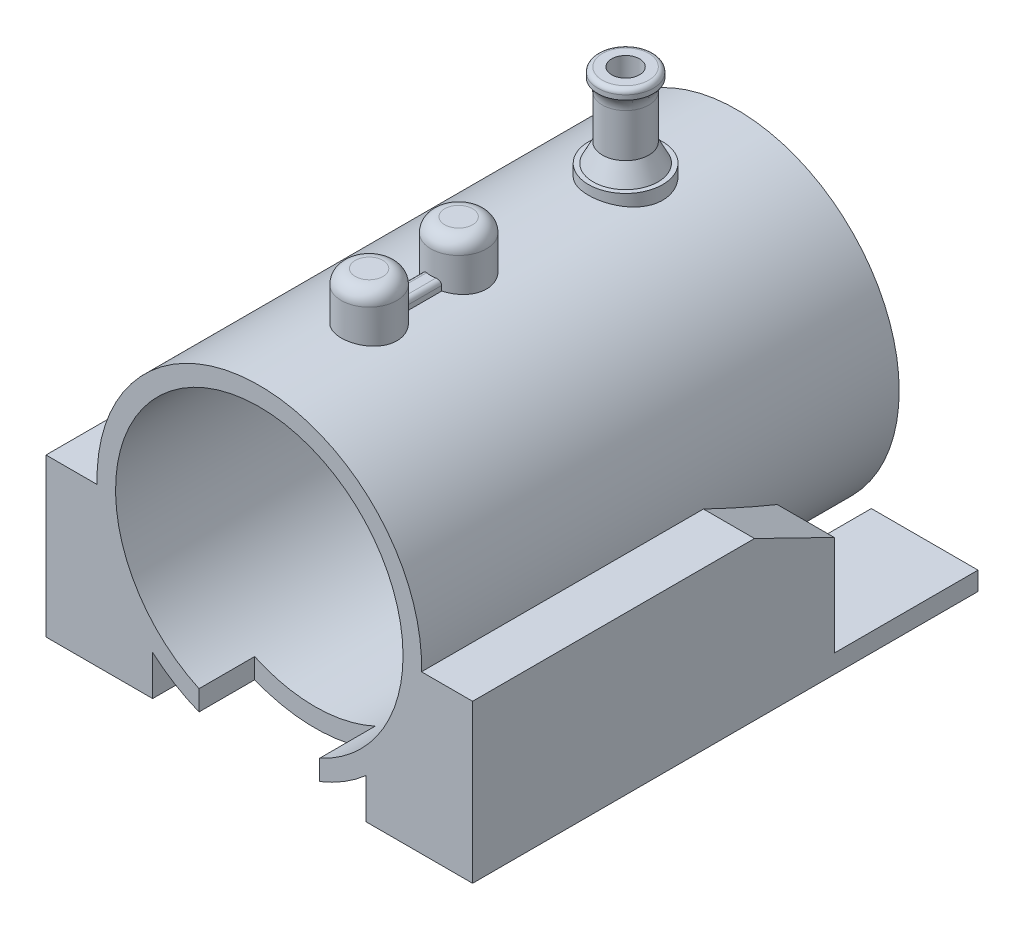
SolidWorks part; units mm, degrees
note: The reader was unsure of these and kept them because the rebuilt part matched: shared geometry of "草图7<3>", "草图10<5>", "草图10<6>", "草图10<7>".
other "标注1"
sketch "草图3" plane through (-22.25, 4, -10) normal (-0.231, 0.6469, -0.7268) x (-0.9696, -0.2151, 0.1167)
ref_plane "前视基准面" through (0, 0, 0) normal (0, 0, 1) x (1, 0, 0)
ref_plane "上视基准面" through (0, 0, 0) normal (0, 1, 0) x (1, 0, 0)
ref_plane "右视基准面" through (0, 0, 0) normal (1, 0, 0) x (0, 0, -1)
other "Configuration Table"
sketch "草图4" plane through (0, 0, 0) normal (0, 0, 1) x (1, 0, 0)
  circle A0 centre (0, 0) radius 17.5
  circle A3 centre (0, 0) radius 13
  dimension "D1" = 35
  dimension "D2" = 26
extrude "凸台-拉伸1" add sketch "草图4" along normal blind 51.5
ref_plane "基准面1" through (-17.5, 0, 0) normal (-1, 0, 0) x (0, 0, 1)
sketch "草图6" plane through (-17.5, 0, 0) normal (-1, 0, 0) x (0, 0, 1)
  line L0 (51.5, -0.5) -> (51.5, -17.5)
  line L1 (51.5, -17.5) -> (51.5, 17.5) construction
  line L2 (51.5, -17.5) -> (-3, -17.5)
  line L3 (0, -17.5) -> (51.5, -17.5) construction
  line L4 (-3, -17.5) -> (-3, -15.5)
  line L5 (-3, -15.5) -> (12.5, -15.5)
  line L6 (12.5, -15.5) -> (12.5, -4.7)
  line L7 (12.5, -4.7) -> (21.1, -0.5)
  line L8 (21.1, -0.5) -> (51.5, -0.5)
  dimension "D1" = 17
  dimension "D2" = 54.5
  dimension "D3" = 30.4
  dimension "D4" = 10.8
  dimension "D5" = 2
  dimension "D6" = 15.5
extrude "凸台-拉伸2" add sketch "草图6" along normal blind 11.5 from offset 6 offset against normal yes
mirror "镜向1" about plane through (0, 0, 0) normal (1, 0, 0) of "凸台-拉伸2"
sketch "草图7" plane through (0, 0, 0) normal (0, 0, -1) x (-1, 0, 0)
  circle A0 centre (0, 0) radius 13
  circle A1 centre (0, 0) radius 9
  dimension "D1" = 26
  dimension "D2" = 18
extrude "凸台-拉伸3" add sketch "草图7" along normal blind 1 contours A0
extrude "凸台-拉伸4" add sketch "草图7<3>" along normal blind 0.6 from surface at 1 contours A1 starting at face at (-13, 0, -1)
sketch "草图7<3>" plane through (0, 0, 0) normal (0, 0, -1) x (-1, 0, 0) same geometry as "草图7"
sketch "草图8" plane through (0, 0, -1.6) normal (0, 0, -1) x (-1, 0, 0)
  line L0 (-12.9783, 0) -> (-10.9783, 0) construction
  line L1 (-12.9783, 0.75) -> (-10.9783, 0.75)
  line L2 (-12.9783, -0.75) -> (-10.9783, -0.75)
  arc A0 (-12.9783, 0.75) -> (-12.9783, -0.75) centre (-12.9783, 0) ccw
  arc A1 (-10.9783, -0.75) -> (-10.9783, 0.75) centre (-10.9783, 0) ccw
  circle A3 centre (0, 0) radius 13 construction
  point P2 (-11.9783, 0)
  dimension "D1" = 2
  dimension "D2" = 1.5
extrude "凸台-拉伸5" add sketch "草图8" against normal up to surface (1.6 mm away) up to face at (-13, 0, 0)
pattern_circular "阵列(圆周)1" count 8 over 360 about axis through (0, 0, 0) along (0, 0, 1) of "凸台-拉伸5"
sketch "草图9" plane through (0, 0, 0) normal (0, 0, -1) x (-1, 0, 0)
  line L0 (10, 3) -> (10, -3) construction
  line L1 (10, -3) -> (14, -3)
  line L2 (10, -3) -> (10, -5.5)
  line L3 (10, -5.5) -> (14, -5.5)
  line L4 (14, -3) -> (14, -5.5)
  line L5 (10, 3) -> (14, 3)
  line L6 (10, 3) -> (10, 5.5)
  line L7 (10, 5.5) -> (14, 5.5)
  line L8 (14, 3) -> (14, 5.5)
  line L9 (10, 0) -> (0, 0) construction
  dimension "D1" = 10
  dimension "D2" = 6
  dimension "D3" = 2.5
  dimension "D4" = 4
extrude "凸台-拉伸6" add sketch "草图9" along normal blind 2
fillet "圆角1" radius 1 2 edges at (-14, -4.25, -2) (-14, 4.25, -2)
fillet "圆角2" radius 0.6 1 edges at (-9, 0, -1.6)
ref_plane "基准面2" through (0, 17.5, 0) normal (0, 1, 0) x (1, 0, 0)
sketch "草图10" plane through (0, 17.5, 0) normal (0, 1, 0) x (1, 0, 0)
  line L0 (0, -32.8284) -> (0, -36.8284) construction
  line L1 (1, -32.8284) -> (-1, -32.8284)
  line L2 (1, -32.8284) -> (1, -36.8284)
  line L3 (1, -36.8284) -> (-1, -36.8284)
  line L4 (-1, -32.8284) -> (-1, -36.8284)
  line L5 (0.75, 0) -> (-0.75, 0) construction
  circle A0 centre (0, -12) radius 4
  circle A1 centre (0, -30) radius 3
  circle A2 centre (0, -39.6569) radius 3
  dimension "D1" = 6
  dimension "D2" = 8
  dimension "D3" = 30
  dimension "D4" = 4
  dimension "D5" = 2
  dimension "D6" = 12
extrude "凸台-拉伸10" add sketch "草图10" against normal up to surface contours A2 | L2 L3 L4 L1 | A1 | A0
extrude "凸台-拉伸11" add sketch "草图10<5>" along normal blind 5 contours A1 | A2
sketch "草图10<5>" plane through (0, 17.5, 0) normal (0, 1, 0) x (1, 0, 0) same geometry as "草图10"
extrude "凸台-拉伸12" add sketch "草图10<6>" along normal blind 1 contours L2 L3 L4 L1
sketch "草图10<6>" plane through (0, 17.5, 0) normal (0, 1, 0) x (1, 0, 0) same geometry as "草图10"
fillet "圆角3" radius 1.5 2 edges at (0, 22.5, 42.6569) (0, 22.5, 33)
fillet "圆角4" radius 0.5 2 edges at (-1, 18.5, 34.8284) (1, 18.5, 34.8284)
extrude "凸台-拉伸13" add sketch "草图10<7>" along normal blind 1 contours A0
sketch "草图10<7>" plane through (0, 17.5, 0) normal (0, 1, 0) x (1, 0, 0) same geometry as "草图10"
sketch "草图11" plane through (0, 18.5, 0) normal (0, 1, 0) x (1, 0, 0)
  circle A0 centre (0, -12) radius 2.5
  circle A1 centre (0, -12) radius 4 construction
  dimension "D1" = 5
extrude "凸台-拉伸14" add sketch "草图11" along normal blind 8
chamfer "倒角2" distance 1 distance2 2 1 edges at (0, 18.5, 14.5)
sketch "草图12" plane through (0, 26.5, 0) normal (0, 1, 0) x (1, 0, 0)
  circle A0 centre (0, -12) radius 3
  circle A1 centre (0, -12) radius 2.5 construction
  dimension "D1" = 6
extrude "凸台-拉伸16" add sketch "草图12" along normal blind 1
fillet "圆角6" radius 2 1 edges at (0, 26.5, 14.5)
fillet "圆角7" radius 0.5 1 edges at (0, 27.5, 15)
sketch "草图13" plane through (0, 27.5, 0) normal (0, 1, 0) x (1, 0, 0)
  circle A0 centre (0, -12) radius 1.5
  circle A1 centre (0, -12) radius 3 construction
  dimension "D1" = 3
extrude "切除-拉伸1" cut sketch "草图13" against normal blind 10
sketch "草图14" plane through (0, 0, 51.5) normal (0, 0, 1) x (1, 0, 0)
  circle A0 centre (0, 0) radius 15.5
  arc A1 (17.4929, -0.5) -> (-17.4929, -0.5) centre (0, 0) ccw construction
  dimension "D1" = 2
extrude "切除-拉伸2" cut sketch "草图14" against normal offset from surface (49.5 mm away) 2 up to face at (17.5, 0, 0)
sketch "草图15" plane through (0, 0, 51.5) normal (0, 0, 1) x (1, 0, 0)
  line L1 (-6.5, -14.0712) -> (6.5, -14.0712)
  line L2 (-6.5, -14.0712) -> (-6.5, -17.5)
  line L3 (-6.5, -17.5) -> (6.5, -17.5)
  line L4 (6.5, -14.0712) -> (6.5, -17.5)
  circle A0 centre (0, 0) radius 15.5 construction
  arc A2 (-11.5, -13.1909) -> (11.5, -13.1909) centre (0, 0) ccw construction
  point P9 (0, 0)
  point P10 (0, 0)
  point P11 (0, 0)
  dimension "D1" = 13
extrude "切除-拉伸4" cut sketch "草图15" against normal blind 6
sketch "草图16" plane through (0, -17.5, 0) normal (0, -1, 0) x (1, 0, 0)
  line L0 (-17.25, 51.5) -> (-17.25, 41.5) construction
  line L1 (-23, 51.5) -> (-11.5, 51.5) construction
  line L2 (17.25, 51.5) -> (17.25, 41.5) construction
  line L3 (23, 51.5) -> (11.5, 51.5) construction
  line L4 (17.25, 12.5) -> (17.25, 22.5) construction
  line L5 (-23, 12.5) -> (-11.5, 12.5) construction
  line L6 (-17.25, 12.5) -> (-17.25, 22.5) construction
  line L7 (23, 12.5) -> (11.5, 12.5) construction
  circle A0 centre (17.25, 41.5) radius 0.6
  circle A1 centre (-17.25, 41.5) radius 0.6
  circle A2 centre (-17.25, 22.5) radius 0.6
  circle A3 centre (17.25, 22.5) radius 0.6
  point P20 (-17.25, 12.5)
  point P21 (-13.0608, 21.5803)
  dimension "D1" = 1.2
  dimension "D2" = 10
extrude "切除-拉伸5" cut sketch "草图16" against normal blind 2
